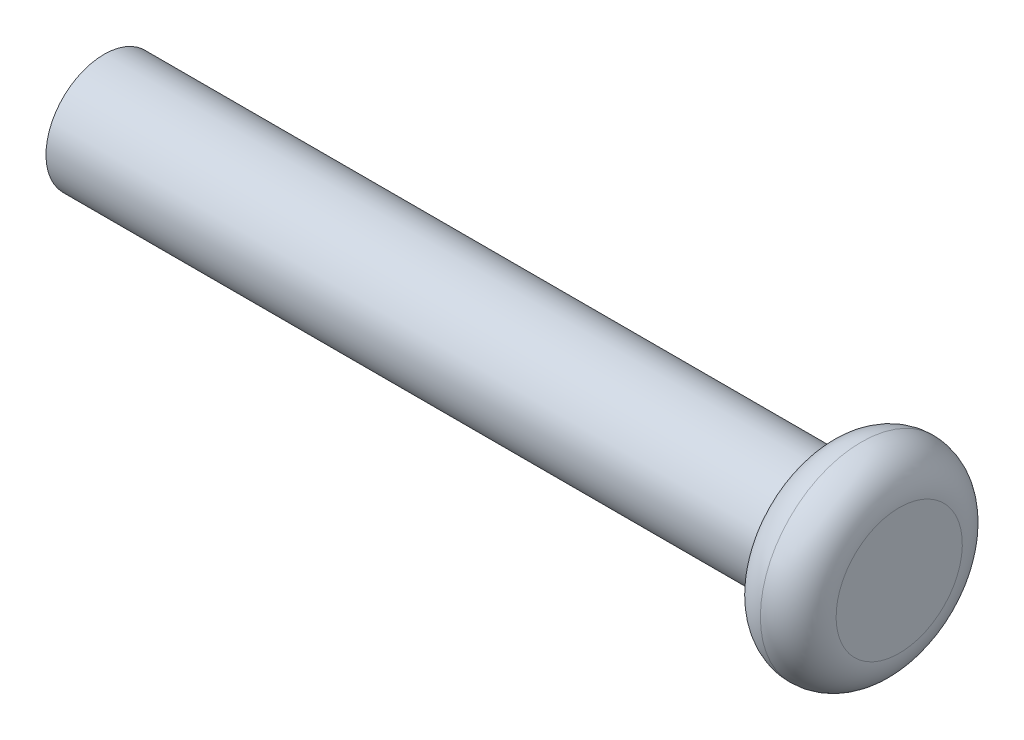
SolidWorks part; units mm, degrees
ref_plane "Front Plane" through (0, 0, 0) normal (0, 0, 1) x (1, 0, 0)
ref_plane "Top Plane" through (0, 0, 0) normal (0, 1, 0) x (1, 0, 0)
ref_plane "Right Plane" through (0, 0, 0) normal (1, 0, 0) x (0, 0, -1)
sketch "Sketch1" plane through (0, 0, 0) normal (0, 0, 1) x (1, 0, 0)
  line L0 (0, 0) -> (0, 4.6)
  line L1 (0, 4.6) -> (57, 4.6)
  line L2 (57, 4.6) -> (57, 8)
  line L3 (57, 8) -> (63, 8)
  line L4 (63, 8) -> (63, 0)
  line L5 (63, 0) -> (0, 0)
  dimension "D1" = 6
  dimension "D2" = 57
  dimension "D3" = 4.6
  dimension "D4" = 8
revolve "Revolve1" add sketch "Sketch1" angle 360 about L5
fillet "Fillet1" radius 3 2 edges at (63, 8, 0) (57, 8, 0)
